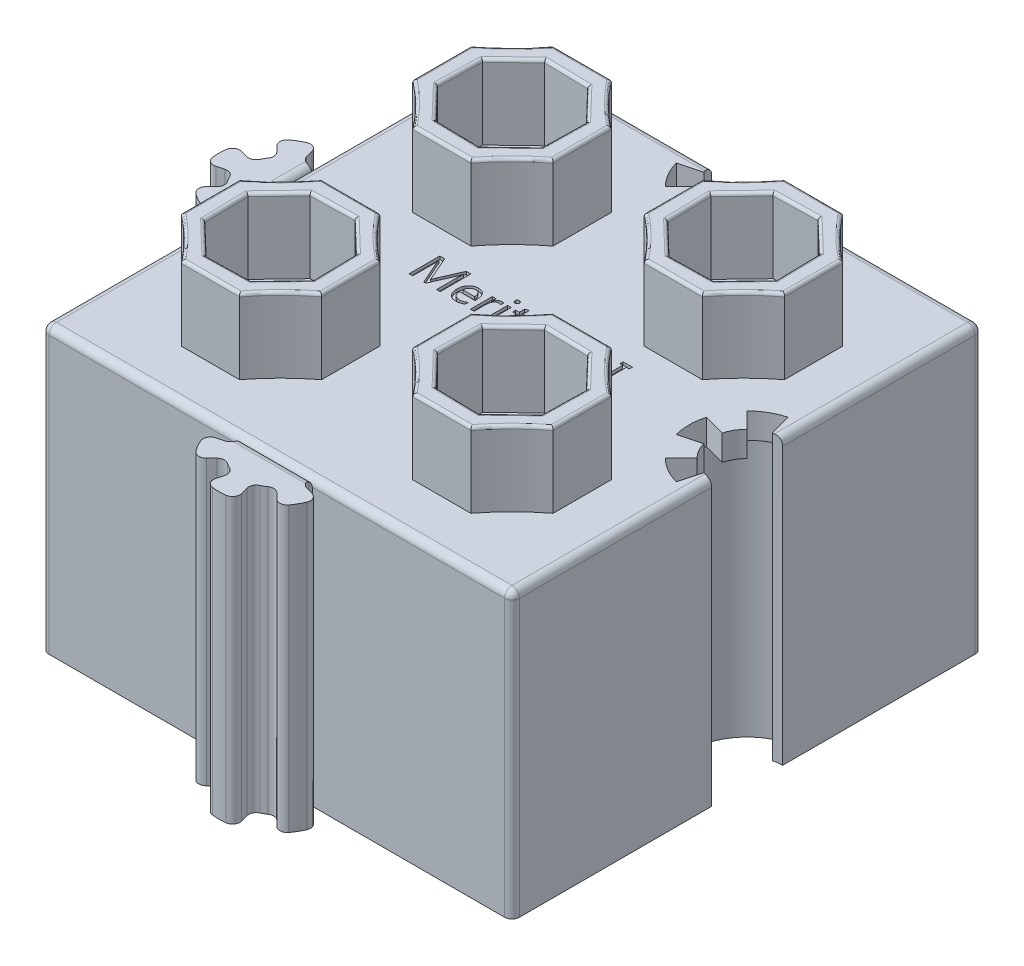
SolidWorks part; units mm, degrees
ref_plane "Front Plane" through (0, 0, 0) normal (0, 0, 1) x (1, 0, 0)
ref_plane "Top Plane" through (0, 0, 0) normal (0, 1, 0) x (1, 0, 0)
ref_plane "Right Plane" through (0, 0, 0) normal (1, 0, 0) x (0, 0, -1)
sketch "Sketch2" plane through (0, 0, 0) normal (0, 1, 0) x (1, 0, 0)
  line L1 (-15.75, 15.75) -> (15.75, 15.75)
  line L2 (-15.75, 15.75) -> (-15.75, -15.75)
  line L3 (-15.75, -15.75) -> (15.75, -15.75)
  line L4 (15.75, 15.75) -> (15.75, -15.75)
  line L5 (-15.75, 15.75) -> (15.75, -15.75) construction
  line L6 (-15.75, -15.75) -> (15.75, 15.75) construction
  point P0 (0, 0)
  dimension "D1" = 31.5
  dimension "D2" = 31.5
extrude "Boss-Extrude1" add sketch "Sketch2" along normal blind 19
sketch "Sketch3" plane through (0, 19, 0) normal (0, 1, 0) x (1, 0, 0)
  line L0 (-13.2, 0) -> (13.2, 0) construction
  line L1 (-9.296, -4.2282) -> (-6.3529, -4.1665)
  line L2 (-11.3335, -6.3529) -> (-9.296, -4.2282)
  line L3 (-11.2718, -9.296) -> (-11.3335, -6.3529)
  line L4 (-9.1471, -11.3335) -> (-11.2718, -9.296)
  line L5 (-6.204, -11.2718) -> (-9.1471, -11.3335)
  line L6 (-4.1665, -9.1471) -> (-6.204, -11.2718)
  line L7 (-4.2282, -6.204) -> (-4.1665, -9.1471)
  line L8 (-6.3529, -4.1665) -> (-4.2282, -6.204)
  line L9 (-9.6968, -3.05) -> (-5.8032, -3.05)
  line L10 (-12.45, -9.6968) -> (-12.45, -5.8032)
  line L11 (-5.8032, -12.45) -> (-9.6968, -12.45)
  line L30 (-3.05, 5.8032) -> (-3.05, 9.6968)
  line L32 (-5.8032, 12.45) -> (-9.6968, 12.45)
  line L34 (-12.45, 9.6968) -> (-12.45, 5.8032)
  line L36 (-9.6968, 3.05) -> (-5.8032, 3.05)
  line L37 (-3.05, -5.8032) -> (-3.05, -9.6968)
  line L46 (0, -13.2) -> (0, 13.2) construction
  line L64 (-6.3529, 4.1665) -> (-4.2282, 6.204)
  line L65 (-4.2282, 6.204) -> (-4.1665, 9.1471)
  line L66 (-4.1665, 9.1471) -> (-6.204, 11.2718)
  line L67 (-6.204, 11.2718) -> (-9.1471, 11.3335)
  line L68 (-9.1471, 11.3335) -> (-11.2718, 9.296)
  line L69 (-11.2718, 9.296) -> (-11.3335, 6.3529)
  line L70 (-11.3335, 6.3529) -> (-9.296, 4.2282)
  line L71 (-9.296, 4.2282) -> (-6.3529, 4.1665)
  line L72 (9.296, 4.2282) -> (6.3529, 4.1665)
  line L73 (11.3335, 6.3529) -> (9.296, 4.2282)
  line L74 (11.2718, 9.296) -> (11.3335, 6.3529)
  line L75 (9.1471, 11.3335) -> (11.2718, 9.296)
  line L76 (6.204, 11.2718) -> (9.1471, 11.3335)
  line L77 (4.1665, 9.1471) -> (6.204, 11.2718)
  line L78 (4.2282, 6.204) -> (4.1665, 9.1471)
  line L79 (6.3529, 4.1665) -> (4.2282, 6.204)
  line L80 (3.05, -5.8032) -> (3.05, -9.6968)
  line L81 (9.6968, 3.05) -> (5.8032, 3.05)
  line L82 (12.45, 9.6968) -> (12.45, 5.8032)
  line L83 (5.8032, 12.45) -> (9.6968, 12.45)
  line L84 (3.05, 5.8032) -> (3.05, 9.6968)
  line L85 (5.8032, -12.45) -> (9.6968, -12.45)
  line L86 (12.45, -9.6968) -> (12.45, -5.8032)
  line L87 (9.6968, -3.05) -> (5.8032, -3.05)
  line L88 (6.3529, -4.1665) -> (4.2282, -6.204)
  line L89 (4.2282, -6.204) -> (4.1665, -9.1471)
  line L90 (4.1665, -9.1471) -> (6.204, -11.2718)
  line L91 (6.204, -11.2718) -> (9.1471, -11.3335)
  line L92 (9.1471, -11.3335) -> (11.2718, -9.296)
  line L93 (11.2718, -9.296) -> (11.3335, -6.3529)
  line L94 (11.3335, -6.3529) -> (9.296, -4.2282)
  line L95 (9.296, -4.2282) -> (6.3529, -4.1665)
  arc A4 (-12.45, 9.6968) -> (-9.6968, 12.45) centre (-21.5903, 21.5903) ccw
  arc A5 (-5.8032, 12.45) -> (-3.05, 9.6968) centre (6.0903, 21.5903) ccw
  arc A6 (-12.45, 5.8032) -> (-9.6968, 3.05) centre (-21.5903, -6.0903) cw
  arc A7 (-5.8032, 3.05) -> (-3.05, 5.8032) centre (6.0903, -6.0903) cw
  arc A8 (-5.8032, -3.05) -> (-3.05, -5.8032) centre (6.0903, 6.0903) ccw
  arc A9 (-12.45, -5.8032) -> (-9.6968, -3.05) centre (-21.5903, 6.0903) ccw
  arc A10 (-5.8032, -12.45) -> (-3.05, -9.6968) centre (6.0903, -21.5903) cw
  arc A11 (-12.45, -9.6968) -> (-9.6968, -12.45) centre (-21.5903, -21.5903) cw
  arc A12 (12.45, -9.6968) -> (9.6968, -12.45) centre (21.5903, -21.5903) ccw
  arc A13 (5.8032, -12.45) -> (3.05, -9.6968) centre (-6.0903, -21.5903) ccw
  arc A14 (12.45, -5.8032) -> (9.6968, -3.05) centre (21.5903, 6.0903) cw
  arc A15 (5.8032, -3.05) -> (3.05, -5.8032) centre (-6.0903, 6.0903) cw
  arc A16 (5.8032, 3.05) -> (3.05, 5.8032) centre (-6.0903, -6.0903) ccw
  arc A17 (12.45, 5.8032) -> (9.6968, 3.05) centre (21.5903, -6.0903) ccw
  arc A18 (5.8032, 12.45) -> (3.05, 9.6968) centre (-6.0903, 21.5903) cw
  arc A19 (12.45, 9.6968) -> (9.6968, 12.45) centre (21.5903, 21.5903) cw
  point P23 (-7.75, 7.75)
  point P25 (7.75, 7.75)
  point P26 (7.75, -7.75)
  point P27 (-7.75, -7.75)
sketch "Sketch5" plane through (0, 19, 0) normal (0, 1, 0) x (1, 0, 0)
  line L0 (15.75, 15.75) -> (-15.75, 15.75) construction
  line L1 (0.6147, 13.4559) -> (1.0029, 12.007)
  line L2 (-3.875, 15.75) -> (3.875, 15.75)
  line L3 (-2.2941, 15.1353) -> (-3.743, 14.7471)
  line L4 (-1.6794, 14.0706) -> (-2.74, 13.01)
  line L5 (2.2941, 15.1353) -> (3.743, 14.7471)
  line L6 (-0.6147, 13.4559) -> (-1.0029, 12.007)
  line L7 (1.6794, 14.0706) -> (2.74, 13.01)
  line L8 (0, 15.75) -> (3.875, 15.75)
  line L9 (15.75, 0) -> (15.75, -3.875)
  line L10 (15.75, -15.75) -> (15.75, 15.75) construction
  line L11 (15.75, 0) -> (15.75, 3.875)
  line L12 (15.1353, 2.2941) -> (14.7471, 3.743)
  line L13 (14.0706, 1.6794) -> (13.01, 2.74)
  line L14 (13.01, 2.74) -> (14.0706, 1.6794)
  line L15 (13.4559, 0.6147) -> (12.007, 1.0029)
  line L16 (13.4559, -0.6147) -> (12.007, -1.0029)
  line L17 (15.1353, -2.2941) -> (14.7471, -3.743)
  line L18 (14.0706, -1.6794) -> (13.01, -2.74)
  arc A0 (-3.875, 15.75) -> (3.875, 15.75) centre (0, 15.75) ccw
  arc A1 (-2.375, 15.75) -> (2.375, 15.75) centre (0, 15.75) ccw
  arc A2 (15.75, 3.875) -> (15.75, -3.875) centre (15.75, 0) ccw
  arc A3 (15.75, 2.375) -> (15.75, -2.375) centre (15.75, 0) ccw
  line M12 (15.75, -15.75) -> (15.75, 15.75)
  dimension "D1" = 4.75
  dimension "D4" = 2.375
  dimension "D2" = 3.875
  dimension "D3" = 3.875
extrude "Cut-Extrude6" cut sketch "Sketch5" against normal through all contours A1 L3 A0 L4 | A1 L6 A0 L1 | A1 L7 A0 L5 | A1 L8 L2 | A3 L9 M12 | A3 L12 A2 L13 | A3 L15 A2 L16 | A3 L18 A2 L17
sketch "Sketch6" plane through (0, 19, 0) normal (0, 1, 0) x (1, 0, 0)
  line L0 (-15.75, -15.75) -> (15.75, -15.75) construction
  line L2 (-2.2941, -16.3647) -> (-3.743, -16.7529)
  line L9 (-1.6794, -17.4294) -> (-2.74, -18.49)
  line L10 (-0.6201, -18.0426) -> (-1.0118, -19.4906)
  line L11 (0.6201, -18.0426) -> (1.0118, -19.4906)
  line L12 (1.6794, -17.4294) -> (2.74, -18.49)
  line L13 (2.2941, -16.3647) -> (3.743, -16.7529)
  line L14 (-1, -15.75) -> (1, -15.75)
  line L15 (-2.375, -15.75) -> (2.375, -15.75)
  line L16 (-15.75, 0) -> (-15.75, 2.375)
  line L17 (-15.75, 15.75) -> (-15.75, -15.75) construction
  line L18 (-15.75, 2.375) -> (-15.75, -2.375)
  line L21 (-16.3647, 2.2941) -> (-16.7529, 3.743)
  line L22 (-16.3647, -2.2941) -> (-16.7529, -3.743)
  line L23 (-17.4294, 1.6794) -> (-18.49, 2.74)
  line L24 (-18.0441, 0.6147) -> (-19.493, 1.0029)
  line L25 (-17.4294, -1.6794) -> (-18.49, -2.74)
  line L26 (-18.0441, -0.6147) -> (-19.493, -1.0029)
  line L27 (-15.75, 2.375) -> (-15.75, -2.375)
  arc A4 (-3.743, -16.7529) -> (-2.74, -18.49) centre (0, -15.75) ccw
  arc A5 (-1.0118, -19.4906) -> (1.0118, -19.4906) centre (0, -15.75) ccw
  arc A6 (2.74, -18.49) -> (3.743, -16.7529) centre (0, -15.75) ccw
  arc A12 (-2.375, -15.75) -> (-2.2941, -16.3647) centre (0, -15.75) ccw
  arc A13 (-1.6794, -17.4294) -> (-0.6147, -18.0441) centre (0, -15.75) ccw
  arc A14 (2.2941, -16.3647) -> (2.375, -15.75) centre (0, -15.75) ccw
  arc A15 (0.6201, -18.0426) -> (1.6794, -17.4294) centre (0, -15.75) ccw
  arc A18 (-18.0441, -0.6147) -> (-17.4294, -1.6794) centre (-15.75, 0) ccw
  arc A21 (-16.7529, 3.743) -> (-18.49, 2.74) centre (-15.75, 0) ccw
  arc A22 (-17.4294, 1.6794) -> (-18.0441, 0.6147) centre (-15.75, 0) ccw
  arc A23 (-19.493, 1.0029) -> (-19.493, -1.0029) centre (-15.75, 0) ccw
  arc A24 (-18.49, -2.74) -> (-16.7529, -3.743) centre (-15.75, 0) ccw
  arc A26 (-16.3647, -2.2941) -> (-15.75, -2.375) centre (-15.75, 0) ccw
  arc A27 (-15.75, 2.375) -> (-16.3647, 2.2941) centre (-15.75, 0) ccw
  dimension "D1" = 7.75
  dimension "D3" = 2.375
  dimension "D2" = 3.875
  dimension "D4" = 2.375
extrude "Boss-Extrude5" add sketch "Sketch3" along normal blind 5
sketch "Sketch7" plane through (0, 0, 0) normal (0, -1, 0) x (1, 0, 0)
  line L4 (0.6, 14.3) -> (6.7217, 14.3)
  line L6 (-14.3, 14.3) -> (-14.3, 8.175)
  line L7 (14.3, 14.3) -> (14.3, 8.175)
  line L8 (15.75, 15.75) -> (15.75, 2.375) construction
  line L9 (-15.75, 15.75) -> (15.75, 15.75)
  line L10 (-15.75, 15.75) -> (-15.75, -15.75)
  line L12 (15.75, 15.75) -> (15.75, -15.75)
  line L14 (-15.75, -15.75) -> (-2.958, -15.75)
  line L15 (2.958, -15.75) -> (15.75, -15.75)
  line L16 (14.3, -14.3) -> (8.1717, -14.3)
  line L17 (3.8251, -14.3) -> (3.5839, -14.3)
  line L18 (3.5839, -14.3) -> (6.7217, -14.3)
  line L19 (-14.3, -14.3) -> (-8.175, -14.3)
  line L20 (-14.3, 14.3) -> (-8.175, 14.3)
  line L21 (-0.556, 14.3) -> (-0.556, 8.175)
  line L22 (0.5393, 0.6) -> (6.725, 0.6)
  line L23 (14.3, -0.6) -> (14.3, -6.725)
  line L24 (-14.3, 14.3) -> (-8.175, 14.3)
  line L25 (-14.3, 0.6) -> (-8.175, 0.6)
  line L26 (-14.3, -0.6) -> (-8.175, -0.6)
  line L27 (-14.3, -0.6) -> (-14.3, -6.725)
  line L29 (0.6, 14.3) -> (0.6, 8.175)
  line L30 (-0.556, -0.6) -> (-0.556, -6.725)
  line L31 (0.6, -0.6) -> (0.6, -6.725)
  line L33 (0.5335, -0.6) -> (6.725, -0.6)
  line L34 (12.95, -7.45) -> (12.95, -6.725)
  line L36 (-14.3, -5.275) -> (-14.3, -6.725)
  line L39 (-8.175, 14.3) -> (-8.175, 12.95)
  line L40 (-8.175, 12.95) -> (-6.725, 12.95)
  line L41 (-6.725, 12.95) -> (-6.725, 14.3)
  line L43 (-7.45, 3.2) -> (-8.175, 3.2)
  line L45 (-7.45, 3.2) -> (-6.725, 3.2)
  line L46 (-6.725, 3.2) -> (-6.725, 0.6)
  line L47 (-8.175, -14.3) -> (-8.175, -12.95)
  line L48 (-8.175, -12.95) -> (-6.725, -12.95)
  line L49 (-6.725, -12.95) -> (-6.725, -14.3)
  line L50 (-14.3, -8.175) -> (-14.3, -14.3)
  line L51 (8.1717, 12.95) -> (6.7217, 12.95)
  line L52 (8.1717, -12.95) -> (8.1717, -14.3)
  line L53 (6.7217, 12.95) -> (6.7217, 14.3)
  line L54 (-6.725, -14.3) -> (-3.5839, -14.3)
  line L55 (-14.3, 8.175) -> (-12.95, 8.175)
  line L56 (-12.95, -7.45) -> (-12.95, -8.175)
  line L57 (-14.3, 6.725) -> (-12.95, 6.725)
  line L58 (8.1717, 12.95) -> (8.1717, 14.3)
  line L59 (6.7217, -14.3) -> (3.8251, -14.3)
  line L60 (8.1717, -12.95) -> (6.7217, -12.95)
  line L61 (6.7217, -12.95) -> (6.7217, -14.3)
  line L62 (-12.95, 6.725) -> (-12.95, 8.175)
  line L64 (12.95, 7.45) -> (12.95, 8.175)
  line L65 (12.95, 8.175) -> (14.3, 8.175)
  line L67 (14.3, 6.725) -> (12.95, 6.725)
  line L68 (12.95, 6.725) -> (12.95, 7.45)
  line L69 (12.95, -6.725) -> (14.3, -6.725)
  line L71 (-12.95, -7.45) -> (-12.95, -6.725)
  line L72 (-12.95, -6.725) -> (-14.3, -6.725)
  line L73 (-12.95, -8.175) -> (-14.3, -8.175)
  line L74 (14.3, -8.175) -> (12.95, -8.175)
  line L75 (12.95, -8.175) -> (12.95, -7.45)
  line L76 (-6.725, -3.2) -> (-8.175, -3.2)
  line L77 (-8.175, -3.2) -> (-8.175, -0.6)
  line L78 (-3.2, 7.45) -> (-3.2, 6.725)
  line L79 (-3.2, 6.725) -> (-0.556, 6.725)
  line L80 (3.2, 6.725) -> (3.2, 7.45)
  line L81 (-3.2, 7.45) -> (-3.2, 8.175)
  line L82 (-3.2, 8.175) -> (-0.556, 8.175)
  line L83 (3.2, 8.175) -> (3.2, 7.45)
  line L84 (0, -13.2) -> (0, 13.2) construction
  line L85 (6.725, -3.2) -> (8.175, -3.2)
  line L86 (6.725, 3.2) -> (6.725, 0.6)
  line L87 (8.175, -3.2) -> (8.175, -0.6)
  line L88 (7.45, 3.2) -> (6.725, 3.2)
  line L89 (7.45, 3.2) -> (8.175, 3.2)
  line L90 (13.2, 0) -> (-13.2, 0) construction
  line L91 (-3.2, -7.45) -> (-3.2, -8.175)
  line L92 (-3.2, -7.45) -> (-3.2, -6.725)
  line L93 (3.2, -6.725) -> (3.2, -7.45)
  line L94 (3.2, -8.175) -> (3.2, -7.45)
  line L95 (-3.2, -6.725) -> (-0.556, -6.725)
  line L96 (-3.2, -8.175) -> (-0.556, -8.175)
  line L97 (-6.725, 0.6) -> (-0.5393, 0.6)
  line L98 (-6.725, -0.6) -> (-0.5335, -0.6)
  line L99 (8.175, 0.6) -> (14.3, 0.6)
  line L100 (8.175, -0.6) -> (14.3, -0.6)
  line L101 (-0.556, -8.175) -> (-0.556, -11.9282)
  line L102 (0.6, -8.175) -> (0.6, -11.9471)
  line L103 (-0.556, 6.725) -> (-0.556, 0.6)
  line L104 (0.6, 6.725) -> (0.6, 0.6)
  line L105 (-6.725, -0.6) -> (-6.725, -3.2)
  line L106 (-8.175, 0.6) -> (-8.175, 3.2)
  line L107 (8.175, 0.6) -> (8.175, 3.2)
  line L108 (6.725, -0.6) -> (6.725, -3.2)
  line L109 (0.6, 8.175) -> (3.2, 8.175)
  line L110 (0.6, 6.725) -> (3.2, 6.725)
  line L111 (0.6, -6.725) -> (3.2, -6.725)
  line L112 (0.6, -8.175) -> (3.2, -8.175)
  line L113 (-6.725, 14.3) -> (-0.556, 14.3)
  line L114 (8.1717, 14.3) -> (14.3, 14.3)
  line L115 (14.3, 6.725) -> (14.3, 0.6)
  line L116 (-14.3, 6.725) -> (-14.3, 0.6)
  line L117 (8.1717, -14.3) -> (14.3, -14.3)
  line L118 (14.3, -8.175) -> (14.3, -14.3)
  arc A0 (-3.5531, -14.2036) -> (-3.224, -14.8861) centre (-3.0946, -14.4032) ccw construction
  arc A1 (3.224, -14.8861) -> (3.5531, -14.2036) centre (3.0946, -14.4032) ccw construction
  arc A2 (-0.4373, -11.8998) -> (-0.8639, -12.526) centre (-0.3809, -12.3966) ccw construction
  arc A3 (0.8639, -12.526) -> (0.4373, -11.8998) centre (0.3809, -12.3966) ccw construction
  point P2 (0, 0)
  dimension "D1" = 1.35
  dimension "D4" = 0.725
  dimension "D5" = 0.725
  dimension "D6" = 0.725
extrude "Cut-Extrude8" cut sketch "Sketch7" against normal blind 17.3
fillet "Fillet19" radius 0.1 48 edges at (-7.45, 0, 3.2) (-12.95, 0, 7.45) (-3.2, 0, 7.45) (-7.45, 0, 12.95) (-6.725, 8.65, 3.2) (-8.175, 8.65, 3.2) (-12.95, 8.65, 6.725) (-12.95, 8.65, 8.175) (-3.2, 8.65, 6.725) (-3.2, 8.65, 8.175) (-8.175, 8.65, 12.95) (-6.725, 8.65, 12.95) (7.4467, 0, -12.95) (6.7217, 8.65, -12.95) (8.1717, 8.65, -12.95) (-7.45, 0, -12.95) (-8.175, 8.65, -12.95) (-6.725, 8.65, -12.95) (-3.2, 0, -7.45) (-3.2, 8.65, -8.175) (-3.2, 8.65, -6.725) (12.95, 8.65, -8.175) (12.95, 8.65, -6.725) (12.95, 0, -7.45) (3.2, 0, -7.45) (3.2, 8.65, -8.175) (3.2, 8.65, -6.725) (-12.95, 0, -7.45) (-12.95, 8.65, -8.175) (-12.95, 8.65, -6.725) (6.725, 8.65, -3.2) (8.175, 8.65, -3.2) (7.45, 0, -3.2) (-8.175, 8.65, -3.2) (-6.725, 8.65, -3.2) (-7.45, 0, -3.2) (8.175, 8.65, 3.2) (6.7217, 8.65, 12.95) (8.1717, 8.65, 12.95) (7.4467, 0, 12.95) (3.2, 0, 7.45) (3.2, 8.65, 8.175) (3.2, 8.65, 6.725) (7.45, 0, 3.2) (6.725, 8.65, 3.2) (12.95, 8.65, 6.725) (12.95, 8.65, 8.175) (12.95, 0, 7.45)
fillet "Fillet20" radius 0.5 10 edges at (15.75, 9.5, 15.75) (15.75, 9.5, -15.75) (-15.75, 9.5, -15.75) (-15.75, 9.5, 15.75) (-9.0625, 19, -15.75) (9.0625, 19, -15.75) (15.75, 19, 9.0625) (15.75, 19, -9.0625) (0, 19, 15.75) (-15.75, 19, 0)
fillet "Fillet21" radius 0.2 64 edges at (10.9837, 24, -4.5163) (12.45, 24, -7.75) (10.9837, 24, -10.9837) (7.75, 24, -12.45) (4.5163, 24, -10.9837) (3.05, 24, -7.75) (4.5163, 24, -4.5163) (7.75, 24, -3.05) (7.8244, 24, -4.1974) (10.3147, 24, -5.2905) (11.3026, 24, -7.8244) (10.2095, 24, -10.3147) (7.6756, 24, -11.3026) (5.1853, 24, -10.2095) (4.1974, 24, -7.6756) (5.2905, 24, -5.1853) (11.3026, 24, 7.8244) (10.3147, 24, 5.2905) (7.8244, 24, 4.1974) (5.2905, 24, 5.1853) (5.1853, 24, 10.2095) (4.1974, 24, 7.6756) (7.6756, 24, 11.3026) (10.2095, 24, 10.3147) (10.9837, 24, 10.9837) (12.45, 24, 7.75) (10.9837, 24, 4.5163) (7.75, 24, 3.05) (4.5163, 24, 4.5163) (3.05, 24, 7.75) (7.75, 24, 12.45) (4.5163, 24, 10.9837) (-10.9837, 24, 10.9837) (-10.9837, 24, 4.5163) (-12.45, 24, 7.75) (-7.75, 24, 12.45) (-7.6756, 24, 11.3026) (-10.2095, 24, 10.3147) (-11.3026, 24, 7.8244) (-10.3147, 24, 5.2905) (-4.5163, 24, 10.9837) (-5.1853, 24, 10.2095) (-4.1974, 24, 7.6756) (-3.05, 24, 7.75) (-4.5163, 24, 4.5163) (-5.2905, 24, 5.1853) (-7.8244, 24, 4.1974) (-7.75, 24, 3.05) (-10.3147, 24, -5.2905) (-11.3026, 24, -7.8244) (-10.2095, 24, -10.3147) (-7.6756, 24, -11.3026) (-5.1853, 24, -10.2095) (-4.1974, 24, -7.6756) (-7.8244, 24, -4.1974) (-5.2905, 24, -5.1853) (-4.5163, 24, -4.5163) (-7.75, 24, -3.05) (-10.9837, 24, -4.5163) (-12.45, 24, -7.75) (-10.9837, 24, -10.9837) (-7.75, 24, -12.45) (-4.5163, 24, -10.9837) (-3.05, 24, -7.75)
extrude "Boss-Extrude7" add sketch "Sketch6" against normal through all
fillet "Fillet24" radius 0.5 24 edges at (2.2941, 9.5, 16.3647) (3.743, 9.5, 16.7529) (2.74, 9.5, 18.49) (1.6794, 9.5, 17.4294) (0.6201, 9.5, 18.0426) (1.0118, 9.5, 19.4906) (-1.0118, 9.5, 19.4906) (-0.6201, 9.5, 18.0426) (-1.6794, 9.5, 17.4294) (-2.74, 9.5, 18.49) (-3.743, 9.5, 16.7529) (-2.2941, 9.5, 16.3647) (-16.3647, 9.5, 2.2941) (-16.7529, 9.5, 3.743) (-18.49, 9.5, 2.74) (-17.4294, 9.5, 1.6794) (-18.0441, 9.5, 0.6147) (-19.493, 9.5, 1.0029) (-19.493, 9.5, -1.0029) (-18.0441, 9.5, -0.6147) (-17.4294, 9.5, -1.6794) (-16.3647, 9.5, -2.2941) (-16.7529, 9.5, -3.743) (-18.49, 9.5, -2.74)
sketch "Sketch10" plane through (0, 19, 0) normal (0, 1, 0) x (1, 0, 0)
  line L0 (15.75, 4.35) -> (15.75, 4)
  line L9 (15.75, -4) -> (15.75, -4.35)
  line L21 (-4.35, 15.75) -> (-4, 15.75)
  line L22 (4, 15.75) -> (4.35, 15.75)
  arc A9 (15.75, 4) -> (15.75, -4) centre (15.75, 0) ccw
  arc A10 (15.75, 4.35) -> (15.75, -4.35) centre (15.75, 0) ccw
  arc A21 (-4, 15.75) -> (4, 15.75) centre (0, 15.75) ccw
  arc A22 (-4.35, 15.75) -> (4.35, 15.75) centre (0, 15.75) ccw
  dimension "D1" = 8
  dimension "D2" = 8.7
  dimension "D3" = 8
  dimension "D4" = 8.7
extrude "Boss-Extrude9" add sketch "Sketch10" against normal through all from offset 0.5 offset against normal yes
sketch "Sketch11" plane through (0, 19, 0) normal (0, 1, 0) x (1, 0, 0)
  line L0 (13.3898, -2.3602) -> (14.0706, -1.6794)
  line L1 (13.3898, 2.3602) -> (14.0706, 1.6794)
  line L2 (-2.3602, 13.3898) -> (-1.6794, 14.0706)
  line L3 (12.4037, -0.8809) -> (13.4559, -0.6147)
  line L4 (12.526, 0.8639) -> (13.5132, 0.5994)
  line L5 (13.4559, 0.6147) -> (12.007, 1.0029) construction
  line L6 (0.6147, 13.4559) -> (0.8639, 12.526)
  line L7 (-0.8639, 12.526) -> (-0.6147, 13.4559)
  line L8 (-0.6147, 13.4559) -> (-1.0029, 12.007) construction
  line L9 (1.6794, 14.0706) -> (2.5128, 13.2855)
  arc A0 (13.3898, 2.3602) -> (13.3915, 3.0746) centre (13.7462, 2.7165) cw
  arc A1 (2.3602, 13.3898) -> (3.1157, 13.4461) centre (2.7137, 13.7434) ccw construction
  arc A2 (12.526, 0.8639) -> (11.8998, 0.4373) centre (12.3966, 0.3809) ccw
  arc A3 (11.8998, -0.4373) -> (12.4037, -0.8809) centre (12.3039, -0.4862) ccw
  arc A4 (13.3898, -2.3602) -> (13.4461, -3.1157) centre (13.7434, -2.7137) ccw
  arc A5 (11.8998, -0.4373) -> (13.4461, -3.1157) centre (15.8677, 0.068) ccw
  arc A6 (13.5132, 0.5994) -> (14.0706, 1.6794) centre (15.8677, 0.068) cw
  arc A7 (11.8998, -0.4373) -> (13.4461, -3.1157) centre (15.75, 0) ccw
  arc A8 (13.4559, -0.6147) -> (14.0706, -1.6794) centre (15.75, 0) ccw
  arc A9 (11.8998, -0.4373) -> (12.526, -0.8639) centre (12.3966, -0.3809) ccw construction
  arc A10 (13.3915, 3.0746) -> (11.8998, 0.4373) centre (15.75, 0) ccw
  arc A11 (-3.1157, 13.4461) -> (-0.4373, 11.8998) centre (0, 15.75) ccw
  arc A12 (-1.6794, 14.0706) -> (-0.6147, 13.4559) centre (0, 15.75) ccw
  arc A13 (-2.3602, 13.3898) -> (-3.1157, 13.4461) centre (-2.7137, 13.7434) cw
  arc A14 (2.5128, 13.2855) -> (3.1157, 13.4461) centre (2.7137, 13.7434) ccw
  arc A15 (-0.8639, 12.526) -> (-0.4373, 11.8998) centre (-0.3809, 12.3966) ccw
  arc A16 (0.8639, 12.526) -> (0.4373, 11.8998) centre (0.3809, 12.3966) cw
  arc A17 (-3.1157, 13.4461) -> (-0.4373, 11.8998) centre (0, 15.75) ccw
  arc A18 (0.6147, 13.4559) -> (1.6794, 14.0706) centre (0, 15.75) ccw
  arc A19 (0.4373, 11.8998) -> (3.1157, 13.4461) centre (0, 15.75) ccw
fillet "Fillet31" radius 0.5 2 edges at (0, 19, 15.75) (-15.75, 19, 0)
sketch "Sketch14" plane through (0, 19, 0) normal (0, 1, 0) x (1, 0, 0)
  text T0 "Meritus AI" font "Ebrima" height in points 8
extrude "Cut-Extrude9" cut sketch "Sketch14" against normal blind 0.2
